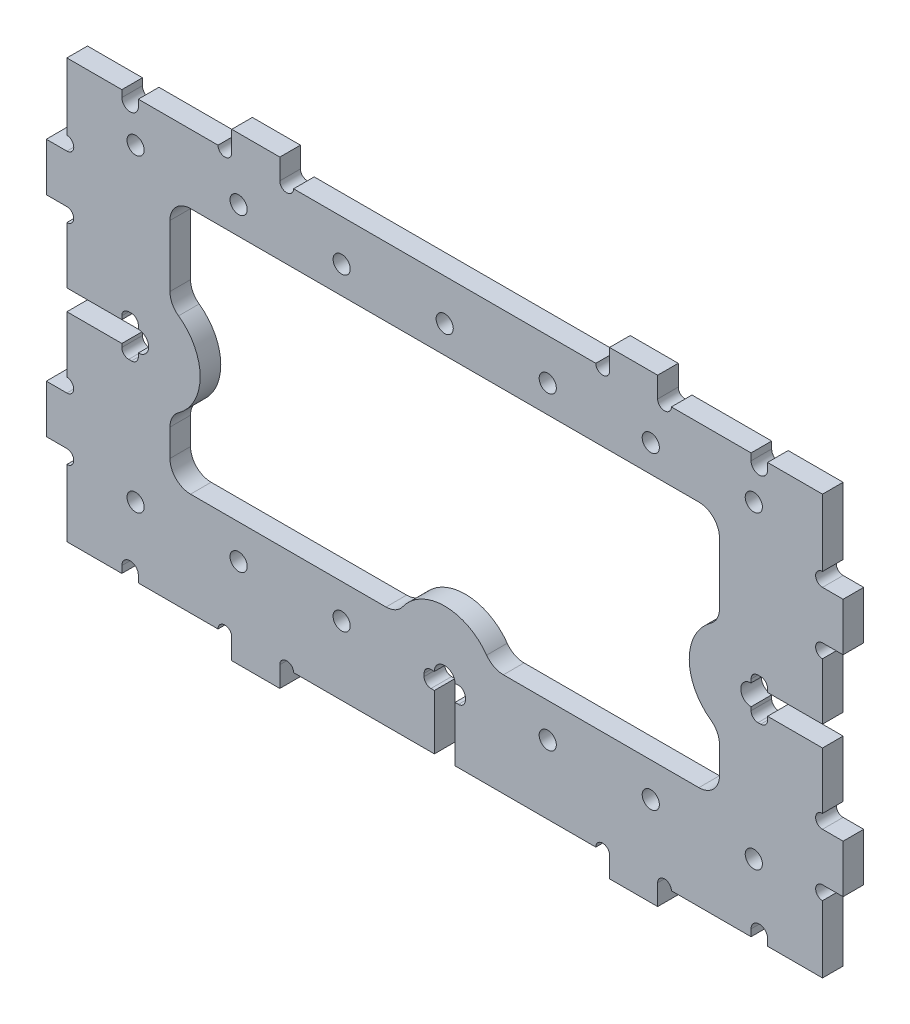
SolidWorks part; units mm, degrees
material "Acrylic (Medium-high impact)"
ref_plane "Front Plane" through (0, 0, 0) normal (0, 0, 1) x (1, 0, 0)
ref_plane "Top Plane" through (0, 0, 0) normal (0, 1, 0) x (1, 0, 0)
ref_plane "Right Plane" through (0, 0, 0) normal (1, 0, 0) x (0, 0, -1)
sketch "Sketch1" plane through (0, 0, 0) normal (0, 0, 1) x (1, 0, 0)
  line L0 (0, 30.5) -> (0, -30.5) construction
  line L1 (-55, 30.5) -> (55, 30.5)
  line L2 (-55, 30.5) -> (-55, -30.5)
  line L3 (-55, -30.5) -> (55, -30.5)
  line L4 (55, 30.5) -> (55, -30.5)
  line L5 (-55, 0) -> (55, 0) construction
  line L6 (-55, 0) -> (-55, -1.5) construction
  line L7 (-55, -1.5) -> (-47, -1.5)
  line L8 (-47, -1.5) -> (-47, -3)
  line L9 (-47, -3) -> (-44.6, -3)
  line L10 (-44.6, -3) -> (-44.6, -1.5)
  line L11 (-44.6, 3) -> (-47, 3)
  line L12 (-47, 3) -> (-47, 1.5)
  line L13 (-47, 1.5) -> (-55, 1.5)
  line L14 (-55, 1.5) -> (-55, -1.5)
  line L15 (-44.6, 1.5) -> (-44.6, 3)
  line L16 (44.6, 1.5) -> (44.6, 3)
  line L17 (47, 3) -> (47, 1.5)
  line L18 (44.6, 3) -> (47, 3)
  line L19 (44.6, -3) -> (44.6, -1.5)
  line L20 (47, -3) -> (44.6, -3)
  line L21 (47, -1.5) -> (47, -3)
  line L22 (47, 1.5) -> (55, 1.5)
  line L23 (55, -1.5) -> (47, -1.5)
  line L24 (55, 1.5) -> (55, -1.5)
  arc A0 (-44.6, -1.5) -> (-44.6, 1.5) centre (-44.6, 0) ccw
  arc A1 (-45.8, 2.9798) -> (-47, 2) centre (-46, 2) ccw
  arc A2 (-44.6, 2) -> (-45.8, 2.9798) centre (-45.6, 2) ccw
  arc A3 (-47, -2) -> (-45.8, -2.9798) centre (-46, -2) ccw
  arc A4 (-45.8, -2.9798) -> (-44.6, -2) centre (-45.6, -2) ccw
  arc A5 (45.8, -2.9798) -> (44.6, -2) centre (45.6, -2) cw
  arc A6 (47, -2) -> (45.8, -2.9798) centre (46, -2) cw
  arc A7 (44.6, 2) -> (45.8, 2.9798) centre (45.6, 2) cw
  arc A8 (45.8, 2.9798) -> (47, 2) centre (46, 2) cw
  arc A9 (44.6, -1.5) -> (44.6, 1.5) centre (44.6, 0) cw
  point P8 (0, 0)
  point P9 (110, 0)
extrude "Boss-Extrude1" add sketch "Sketch1" along normal blind 3 contours L19 A9 L16 L18 L17 L22 L4 L1 L2 L13 L12 L11 L15 A0 L10 L9 L8 L7 L3 L23 L21 L20 | A3 L8 L9 | A4 L9 L10 | A2 L15 L11 | A1 L11 L12 | L20 A5 L19 | L21 A6 L20 | L18 A8 L17 | L16 A7 L18 region at (0, 0, 0) region at (-46.7766, 2.7766, 0) region at (46.7766, 2.7766, 0) region at (-46.7766, -2.7766, 0) region at (46.7766, -2.7766, 0) region at (-44.8234, 2.7766, 0) region at (44.8234, 2.7766, 0) region at (-44.8234, -2.7766, 0) region at (44.8234, -2.7766, 0)
sketch "Sketch2" plane through (0, 0, 3) normal (0, 0, 1) x (1, 0, 0)
  line L0 (-47, -1.5) -> (-47, -30.5) construction
  line L1 (-55, -30.5) -> (55, -30.5) construction
  line L2 (-47, -30.5) -> (-44.6, -30.5) construction
  line L3 (-44.6, -30.5) -> (-44.6, 30.5) construction
  line L4 (-55, 30.5) -> (55, 30.5) construction
  line L5 (-44.6, 30.5) -> (-47, 30.5) construction
  line L6 (-47, 30.5) -> (-47, -1.5) construction
  line L7 (47, -1.5) -> (47, -30.5) construction
  line L8 (47, -30.5) -> (44.6, -30.5) construction
  line L9 (44.6, -30.5) -> (44.6, 30.5) construction
  line L10 (44.6, 30.5) -> (47, 30.5) construction
  line L11 (47, 30.5) -> (47, -1.5) construction
  line L12 (-45.8, 30.5) -> (-45.8, 29.5) construction
  line L13 (-45.8, -30.5) -> (-45.8, -29.5) construction
  line L14 (45.8, -30.5) -> (45.8, -29.5) construction
  line L15 (45.8, 30.5) -> (45.8, 29.5) construction
  line L16 (-47, 29.5) -> (-47, 30.5)
  line L17 (-47, 30.5) -> (-44.6, 30.5)
  line L18 (-44.6, 30.5) -> (-44.6, 29.5)
  line L19 (-47, -29.5) -> (-47, -30.5)
  line L20 (-47, -30.5) -> (-44.6, -30.5)
  line L21 (-44.6, -30.5) -> (-44.6, -29.5)
  line L22 (44.6, -29.5) -> (44.6, -30.5)
  line L23 (44.6, -30.5) -> (47, -30.5)
  line L24 (47, -30.5) -> (47, -29.5)
  line L25 (44.6, 29.5) -> (44.6, 30.5)
  line L26 (44.6, 30.5) -> (47, 30.5)
  line L27 (47, 30.5) -> (47, 29.5)
  arc A0 (44.6, 29.5) -> (47, 29.5) centre (45.8, 29.5) ccw
  arc A1 (-46.4633, -30.5) -> (-45.1367, -30.5) centre (-45.8, -29.5) ccw
  arc A2 (45.1367, -30.5) -> (46.4633, -30.5) centre (45.8, -29.5) ccw
  arc A3 (-47, 29.5) -> (-44.6, 29.5) centre (-45.8, 29.5) ccw
  arc A4 (46.4633, 30.5) -> (45.1367, 30.5) centre (45.8, 29.5) ccw
  arc A5 (47, -29.5) -> (44.6, -29.5) centre (45.8, -29.5) ccw
  arc A6 (-44.6, -29.5) -> (-47, -29.5) centre (-45.8, -29.5) ccw
  arc A7 (-45.1367, 30.5) -> (-46.4633, 30.5) centre (-45.8, 29.5) ccw
  line M11 (55, 30.5) -> (-55, 30.5)
  line M27 (-55, -30.5) -> (55, -30.5)
extrude "Cut-Extrude1" cut sketch "Sketch2" against normal blind 3 contours L25 A0 L27 L26 M11 | L24 A5 L22 L23 M27 | L21 A6 L19 L20 M27 | L16 A3 L18 L17 M11 region at (45.8, 29.5103, 3) region at (-45.8, 29.5103, 3) region at (-45.8, -29.5103, 3) region at (45.8, -29.5103, 3)
sketch "Sketch3" plane through (0, 0, 3) normal (0, 0, 1) x (1, 0, 0)
  line L0 (0, -19.4735) -> (0, 19.4735) construction
  line L1 (-44.6, 30.5) -> (44.6, 30.5) construction
  line L2 (-43.1, 0) -> (43.1, 0) construction
  line L3 (0, 30.5) -> (1.5, 30.5)
  line L4 (1.5, 30.5) -> (1.5, 22.5)
  line L5 (1.5, 22.5) -> (3, 22.5)
  line L6 (3, 22.5) -> (3, 20.1)
  line L7 (3, 20.1) -> (1.5, 20.1)
  line L8 (-3, 20.1) -> (-3, 22.5)
  line L9 (-3, 22.5) -> (-1.5, 22.5)
  line L10 (-1.5, 22.5) -> (-1.5, 30.5)
  line L11 (-1.5, 30.5) -> (1.5, 30.5)
  line L12 (-1.5, 20.1) -> (-3, 20.1)
  line L13 (-1.5, -20.1) -> (-3, -20.1)
  line L14 (-1.5, -30.5) -> (1.5, -30.5)
  line L15 (-1.5, -22.5) -> (-1.5, -30.5)
  line L16 (-3, -22.5) -> (-1.5, -22.5)
  line L17 (-3, -20.1) -> (-3, -22.5)
  line L18 (3, -20.1) -> (1.5, -20.1)
  line L19 (3, -22.5) -> (3, -20.1)
  line L20 (1.5, -22.5) -> (3, -22.5)
  line L21 (1.5, -30.5) -> (1.5, -22.5)
  line L22 (0, -30.5) -> (1.5, -30.5)
  arc A0 (-44.6, -1.5) -> (-44.6, 1.5) centre (-44.6, 0) ccw construction
  arc A1 (44.6, 1.5) -> (44.6, -1.5) centre (44.6, 0) ccw construction
  arc A2 (-1.5, 20.1) -> (1.5, 20.1) centre (0, 20.1) ccw
  arc A3 (-1.5, -20.1) -> (1.5, -20.1) centre (0, -20.1) cw
  point P26 (0, 0)
  line M23 (-44.6, -30.5) -> (44.6, -30.5)
extrude "Cut-Extrude3" cut sketch "Sketch3" against normal blind 3 contours A3 L13 L17 L16 L15 L14 L21 L20 L19 L18 M23 region at (0, -24.1213, 3)
fillet "Fillet2" radius 1 4 edges at (-3, -20.1, 1.5) (3, -22.5, 1.5) (3, -20.1, 1.5) (-3, -22.5, 1.5)
sketch "Sketch4" plane through (0, 0, 3) normal (0, 0, 1) x (1, 0, 0)
  line L0 (-55, 1.5) -> (-55, -1.5) construction
  line L1 (55, 1.5) -> (55, -1.5) construction
  line L2 (-1.5, -30.5) -> (1.5, -30.5) construction
  line L3 (-55, 30.5) -> (-40, 30.5)
  line L4 (-44.6, 30.5) -> (44.6, 30.5) construction
  line L5 (-40, 30.5) -> (-40, -15.5)
  line L6 (-40, -15.5) -> (40, -15.5)
  line L7 (40, -15.5) -> (40, 20.5)
  line L8 (40, 20.5) -> (-40, 20.5)
  circle A0 centre (-43.1, 0) radius 7.5
  arc A1 (-44.6, -1.5) -> (-44.6, 1.5) centre (-44.6, 0) ccw construction
  circle A2 centre (0, -18.6) radius 7.5
  arc A3 (1.5, -20.1) -> (-1.5, -20.1) centre (0, -20.1) ccw construction
  circle A4 centre (43.1, 0) radius 7.5
  arc A5 (44.6, 1.5) -> (44.6, -1.5) centre (44.6, 0) ccw construction
extrude "Cut-Extrude4" cut sketch "Sketch4" against normal blind 10 contours A4 L7 L8 L5 A0 L6 A2 region at (0, 2.8329, 3)
fillet "Fillet3" radius 3 10 edges at (40, -6.8293, 1.5) (40, -15.5, 1.5) (6.8293, -15.5, 1.5) (-6.8293, -15.5, 1.5) (-40, -6.8293, 1.5) (-40, 6.8293, 1.5) (40, 20.5, 1.5) (40, 6.8293, 1.5) (-40, -15.5, 1.5) (-40, 20.5, 1.5)
sketch "Sketch5" plane through (0, 0, 3) normal (0, 0, 1) x (1, 0, 0)
  line L0 (-55, -30.5) -> (0, -30.5) construction
  line L1 (0, -30.5) -> (55, -30.5) construction
  line L2 (55, -30.5) -> (55, 0) construction
  line L3 (55, 0) -> (55, 30.5) construction
  line L4 (55, 15.25) -> (58, 15.25) construction
  line L5 (58, 15.25) -> (58, 11.75) construction
  line L6 (58, 11.75) -> (55, 11.75) construction
  line L7 (55, 11.75) -> (55, 18.75) construction
  line L8 (55, 18.75) -> (58, 18.75) construction
  line L9 (58, 18.75) -> (58, 15.25) construction
  line L10 (55, -15.25) -> (58, -15.25) construction
  line L11 (58, -15.25) -> (58, -11.75) construction
  line L12 (58, -11.75) -> (55, -11.75) construction
  line L13 (55, -11.75) -> (55, -18.75) construction
  line L14 (55, -18.75) -> (58, -18.75) construction
  line L15 (58, -18.75) -> (58, -15.25) construction
  line L16 (-27.5, -30.5) -> (-27.5, -33.5) construction
  line L17 (-27.5, -33.5) -> (-24, -33.5) construction
  line L18 (-24, -33.5) -> (-24, -30.5) construction
  line L19 (-24, -30.5) -> (-31, -30.5) construction
  line L20 (-31, -30.5) -> (-31, -33.5) construction
  line L21 (-31, -33.5) -> (-27.5, -33.5) construction
  line L22 (27.5, -30.5) -> (27.5, -33.5) construction
  line L23 (27.5, -33.5) -> (24, -33.5) construction
  line L24 (24, -33.5) -> (24, -30.5) construction
  line L25 (24, -30.5) -> (31, -30.5) construction
  line L26 (31, -30.5) -> (31, -33.5) construction
  line L27 (31, -33.5) -> (27.5, -33.5) construction
  line L28 (-35.6, 0) -> (35.6, 0) construction
  line L29 (0, -11.1) -> (0, 20.5) construction
  line L30 (37, 20.5) -> (-37, 20.5) construction
  line L31 (-58, -18.75) -> (-58, -15.25) construction
  line L32 (-55, -18.75) -> (-58, -18.75) construction
  line L33 (-55, -11.75) -> (-55, -18.75) construction
  line L34 (-58, -11.75) -> (-55, -11.75) construction
  line L35 (-58, -15.25) -> (-58, -11.75) construction
  line L36 (-55, -15.25) -> (-58, -15.25) construction
  line L37 (-58, 18.75) -> (-58, 15.25) construction
  line L38 (-55, 18.75) -> (-58, 18.75) construction
  line L39 (-55, 11.75) -> (-55, 18.75) construction
  line L40 (-58, 11.75) -> (-55, 11.75) construction
  line L41 (-58, 15.25) -> (-58, 11.75) construction
  line L42 (-55, 15.25) -> (-58, 15.25) construction
  line L43 (-55, 0) -> (-55, 30.5) construction
  line L44 (-55, -30.5) -> (-55, 0) construction
  line L45 (31, 33.5) -> (27.5, 33.5) construction
  line L46 (-58, 18.75) -> (-55, 18.75)
  line L47 (-58, 18.75) -> (-58, 11.75)
  line L48 (-58, 11.75) -> (-55, 11.75)
  line L49 (-55, 18.75) -> (-55, 11.75)
  line L50 (-58, -11.75) -> (-55, -11.75)
  line L51 (-58, -11.75) -> (-58, -18.75)
  line L52 (-58, -18.75) -> (-55, -18.75)
  line L53 (-55, -11.75) -> (-55, -18.75)
  line L54 (55, -11.75) -> (58, -11.75)
  line L55 (55, -11.75) -> (55, -18.75)
  line L56 (55, -18.75) -> (58, -18.75)
  line L57 (58, -11.75) -> (58, -18.75)
  line L58 (55, 18.75) -> (58, 18.75)
  line L59 (55, 18.75) -> (55, 11.75)
  line L60 (55, 11.75) -> (58, 11.75)
  line L61 (58, 18.75) -> (58, 11.75)
  line L62 (24, -30.5) -> (31, -30.5)
  line L63 (24, -30.5) -> (24, -33.5)
  line L64 (24, -33.5) -> (31, -33.5)
  line L65 (31, -30.5) -> (31, -33.5)
  line L66 (-31, -30.5) -> (-24, -30.5)
  line L67 (-31, -30.5) -> (-31, -33.5)
  line L68 (-31, -33.5) -> (-24, -33.5)
  line L69 (-24, -30.5) -> (-24, -33.5)
  line L70 (31, 30.5) -> (31, 33.5) construction
  line L71 (24, 30.5) -> (31, 30.5) construction
  line L72 (24, 33.5) -> (24, 30.5) construction
  line L73 (27.5, 33.5) -> (24, 33.5) construction
  line L74 (27.5, 30.5) -> (27.5, 33.5) construction
  line L75 (-31, 33.5) -> (-27.5, 33.5) construction
  line L76 (-31, 30.5) -> (-31, 33.5) construction
  line L77 (-24, 30.5) -> (-31, 30.5) construction
  line L78 (-24, 33.5) -> (-24, 30.5) construction
  line L79 (-27.5, 33.5) -> (-24, 33.5) construction
  line L80 (-27.5, 30.5) -> (-27.5, 33.5) construction
  line L81 (0, 30.5) -> (55, 30.5) construction
  line L82 (-55, 30.5) -> (0, 30.5) construction
  line L83 (-24, 30.5) -> (-24, 33.5)
  line L84 (-31, 33.5) -> (-24, 33.5)
  line L85 (-31, 30.5) -> (-31, 33.5)
  line L86 (-31, 30.5) -> (-24, 30.5)
  line L87 (31, 30.5) -> (31, 33.5)
  line L88 (24, 33.5) -> (31, 33.5)
  line L89 (24, 30.5) -> (24, 33.5)
  line L90 (24, 30.5) -> (31, 30.5)
  arc A0 (-38.7429, -6.1045) -> (-38.7429, 6.1045) centre (-43.1, 0) ccw construction
  arc A1 (38.7429, 6.1045) -> (38.7429, -6.1045) centre (43.1, 0) ccw construction
  arc A2 (6.1045, -14.2429) -> (-6.1045, -14.2429) centre (0, -18.6) ccw construction
extrude "Boss-Extrude2" add sketch "Sketch5" against normal blind 3
sketch "Sketch6" plane through (0, 0, 3) normal (0, 0, 1) x (1, 0, 0)
  line L0 (-24, 30.5) -> (-23, 30.5) construction
  line L1 (-24, 30.5) -> (24, 30.5) construction
  line L2 (-31, 30.5) -> (-32, 30.5) construction
  line L3 (-44.6, 30.5) -> (-31, 30.5) construction
  line L4 (24, 30.5) -> (23, 30.5) construction
  line L5 (31, 30.5) -> (32, 30.5) construction
  line L6 (31, 30.5) -> (44.6, 30.5) construction
  line L7 (55, 18.75) -> (55, 19.75) construction
  line L8 (55, 30.5) -> (55, 18.75) construction
  line L9 (55, 11.75) -> (55, 10.75) construction
  line L10 (55, 11.75) -> (55, 1.5) construction
  line L11 (55, -11.75) -> (55, -10.75) construction
  line L12 (55, -1.5) -> (55, -11.75) construction
  line L13 (55, -18.75) -> (55, -19.75) construction
  line L14 (55, -18.75) -> (55, -30.5) construction
  line L15 (31, -30.5) -> (32, -30.5) construction
  line L16 (31, -30.5) -> (44.6, -30.5) construction
  line L17 (24, -30.5) -> (23, -30.5) construction
  line L18 (1.5, -30.5) -> (24, -30.5) construction
  line L19 (-24, -30.5) -> (-23, -30.5) construction
  line L20 (-24, -30.5) -> (-1.5, -30.5) construction
  line L21 (-31, -30.5) -> (-32, -30.5) construction
  line L22 (-44.6, -30.5) -> (-31, -30.5) construction
  line L23 (-55, -18.75) -> (-55, -19.75) construction
  line L24 (-55, -18.75) -> (-55, -30.5) construction
  line L25 (-55, -11.75) -> (-55, -10.75) construction
  line L26 (-55, -1.5) -> (-55, -11.75) construction
  line L27 (-55, 18.75) -> (-55, 19.75) construction
  line L28 (-55, 30.5) -> (-55, 18.75) construction
  line L29 (-55, 11.75) -> (-55, 10.75) construction
  line L30 (-55, 11.75) -> (-55, 1.5) construction
hole_wizard "Ø2.0 (2) Diameter Hole1" positions "3DSketch2" profile "Sketch8" hole size "Ø2.0" standard "ISO"
sketch3d "3DSketch2"
  point P0 (-23, 30.5, 3)
  point P3 (-32, 30.5, 3)
  point P6 (-55, 19.75, 3)
  point P9 (-55, 10.75, 3)
  point P12 (-55, -10.75, 3)
  point P15 (-55, -19.75, 3)
  point P18 (-32, -30.5, 3)
  point P21 (-23, -30.5, 3)
  point P24 (23, -30.5, 3)
  point P27 (32, -30.5, 3)
  point P30 (55, -19.75, 3)
  point P33 (55, -10.75, 3)
  point P36 (55, 10.75, 3)
  point P39 (55, 19.75, 3)
  point P42 (32, 30.5, 3)
  point P45 (23, 30.5, 3)
sketch "Sketch8" plane through (-23, 30.5, 3) normal (1, 0, 0) x (0, -1, 0)
  line L0 (0, 0) -> (0, 6.6009)
  line L1 (0, 6.6009) -> (1, 6)
  line L2 (1, 6) -> (1, 0)
  line L5 (1, 0) -> (0, 0)
  line L10 (0, 6.6009) -> (-1, 6) construction
  line L11 (0, -6.35) -> (0, 107.95) construction
  dimension "Hole Dia." = 2
  dimension "Hole Depth" = 6
  dimension "Drill Angle" = 118
sketch "Sketch9" plane through (0, 0, 3) normal (0, 0, 1) x (1, 0, 0)
  line L0 (0, 20.5) -> (0, 24.5) construction
  line L1 (37, 20.5) -> (-37, 20.5) construction
  circle A0 centre (0, 24.5) radius 1.25
  circle A1 centre (15, 24.5) radius 1.25
  circle A2 centre (30, 24.5) radius 1.25
  circle A3 centre (45, 24.5) radius 1.25
  circle A4 centre (-15, 24.5) radius 1.25
  circle A5 centre (-30, 24.5) radius 1.25
  circle A6 centre (-45, 24.5) radius 1.25
  circle A7 centre (-15, -20.5) radius 1.25
  circle A8 centre (-30, -20.5) radius 1.25
  circle A9 centre (-45, -20.5) radius 1.25
  circle A10 centre (15, -20.5) radius 1.25
  circle A11 centre (30, -20.5) radius 1.25
  circle A12 centre (45, -20.5) radius 1.25
  dimension "D1" = 4
  dimension "D2" = 4
  dimension "D3" = 2
extrude "Cut-Extrude5" cut sketch "Sketch9" against normal blind 10
